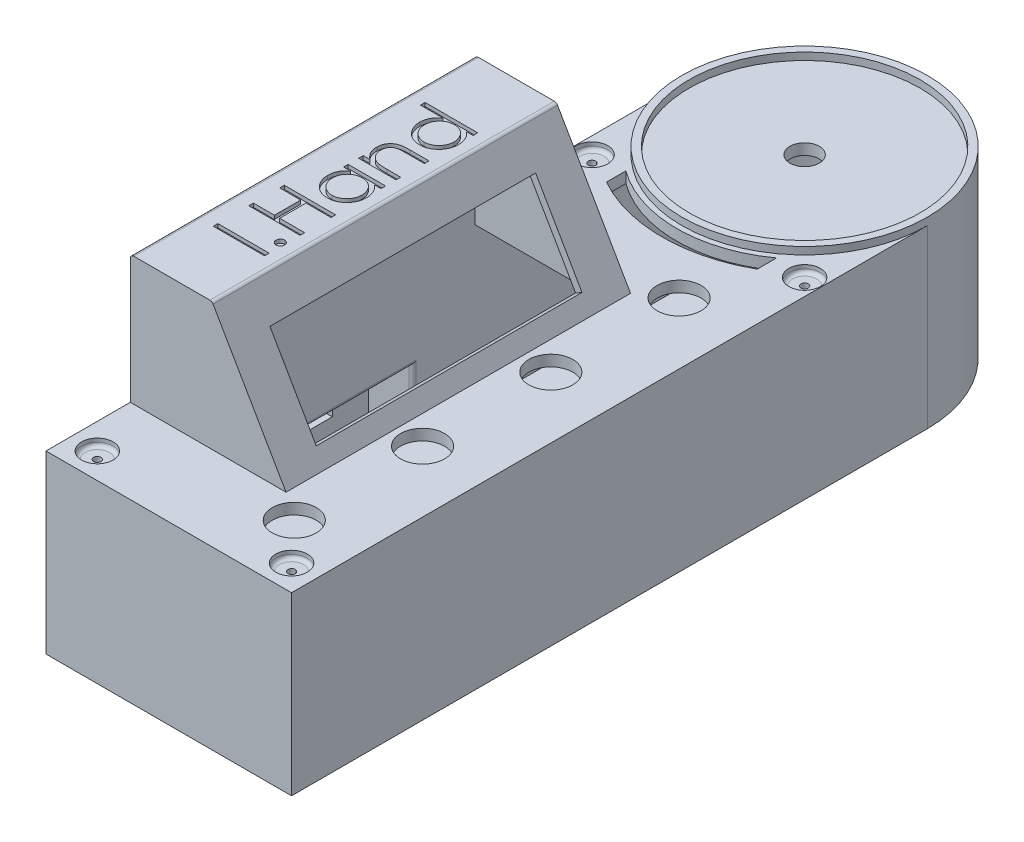
SolidWorks part; units mm, degrees
ref_plane "Front Plane" through (0, 0, 0) normal (0, 0, 1) x (1, 0, 0)
ref_plane "Top Plane" through (0, 0, 0) normal (0, 1, 0) x (1, 0, 0)
ref_plane "Right Plane" through (0, 0, 0) normal (1, 0, 0) x (0, 0, -1)
sketch "Sketch1" plane through (0, 0, 0) normal (0, 0, 1) x (1, 0, 0)
  line L6 (0, 0) -> (0, 47) construction
  line L8 (-31.5, 48) -> (-31.5, 50)
  line L9 (-31.5, 50) -> (-33.5, 50)
  line L10 (-33.5, 50) -> (-33.5, 0)
  line L11 (-33.5, 0) -> (0, 0)
  line L13 (0, 24.8) -> (-8.2, 24.8)
  line L14 (-31.5, 2) -> (-8.2, 2)
  line L17 (-31.5, 45) -> (-31.5, 2)
  line L18 (-8.2, 2) -> (-8.2, 24.8)
  line L19 (0, 0) -> (0, 24.8)
  line L20 (-4, 48) -> (-4, 45)
  line L23 (-31.5, 48) -> (-4, 48)
  line L24 (-31.5, 45) -> (-4, 45)
  dimension "D1" = 33.5
  dimension "D2" = 8
  dimension "D3" = 2
  dimension "D4" = 50
  dimension "D5" = 3
  dimension "D6" = 8.2
  dimension "D7" = 2
  dimension "D8" = 2
  dimension "D9" = 24.8
revolve "Revolve1" add sketch "Sketch1" angle 360 about L6
sketch "Sketch4" plane through (0, 0, 0) normal (0, 0, 1) x (1, 0, 0)
  line L3 (33.5, 0) -> (-33.5, 0)
  line L4 (-31.5, 45) -> (-31.5, 2)
  line L5 (-31.5, 2) -> (31.5, 2)
  line L6 (31.5, 2) -> (31.5, 45)
  line L7 (31.5, 45) -> (-31.5, 45)
  line L8 (31.5, 48) -> (33.5, 48)
  line L9 (-31.5, 48) -> (31.5, 48)
  line L10 (33.5, 48) -> (33.5, 0)
  line L11 (-31.5, 48) -> (-33.5, 48)
  line L12 (-33.5, 48) -> (-33.5, 0)
  dimension "D4" = 2
extrude "Boss-Extrude2" add sketch "Sketch4" along normal blind 173.5
sketch "Sketch6" plane through (0, 48, 0) normal (0, 1, 0) x (1, 0, 0)
  line L0 (4, 0) -> (-4, 0) construction
  circle A0 centre (0, 0) radius 4
extrude "Cut-Extrude1" cut sketch "Sketch6" against normal blind 3
sketch "Sketch9" plane through (0, 0, 173.5) normal (0, 0, 1) x (1, 0, 0)
  line L0 (-31.5, 45) -> (-31.5, 2)
  line L1 (-31.5, 2) -> (31.5, 2)
  line L2 (31.5, 2) -> (31.5, 45)
  line L3 (31.5, 45) -> (-31.5, 45)
extrude "Cut-Extrude2" cut sketch "Sketch9" against normal blind 173.5
sketch "Sketch10" plane through (0, 2, 0) normal (0, 1, 0) x (1, 0, 0)
  line L0 (-8.2, 0) -> (8.2, 0) construction
  circle A0 centre (0, 0) radius 8.2
extrude "Boss-Extrude3" add sketch "Sketch10" along normal blind 22.8
sketch "Sketch11" plane through (0, 0, 173.5) normal (0, 0, 1) x (1, 0, 0)
  line L1 (-31.5, 2) -> (31.5, 2)
  line L2 (-31.5, 2) -> (-31.5, 45)
  line L3 (-31.5, 45) -> (31.5, 45)
  line L4 (31.5, 2) -> (31.5, 45)
extrude "Boss-Extrude4" add sketch "Sketch11" against normal blind 2
sketch "Sketch13" plane through (0, 2, 0) normal (0, 1, 0) x (1, 0, 0)
  line L0 (-26.5, -161.5) -> (-26.5, -171.5)
  line L1 (-31.5, -171.5) -> (-21.5, -171.5)
  line L2 (-31.5, -171.5) -> (-31.5, -161.5)
  line L3 (-31.5, -161.5) -> (-21.5, -161.5)
  line L4 (-21.5, -171.5) -> (-21.5, -161.5)
  line L5 (31.5, -171.5) -> (21.5, -171.5)
  line L6 (31.5, -171.5) -> (31.5, -161.5)
  line L7 (31.5, -161.5) -> (21.5, -161.5)
  line L8 (21.5, -171.5) -> (21.5, -161.5)
  line L9 (-26.5, -171.5) -> (-21.5, -166.5)
  line L10 (-21.5, -166.5) -> (-31.5, -166.5)
  line L11 (26.5, -161.5) -> (26.5, -171.5)
  line L12 (26.5, -171.5) -> (21.5, -166.5)
  line L13 (21.5, -166.5) -> (31.5, -166.5)
  circle A0 centre (-26.5, -166.5) radius 3
  circle A1 centre (26.5, -166.5) radius 3
  dimension "D1" = 10
  dimension "D2" = 10
  dimension "D3" = 10
extrude "Boss-Extrude5" add sketch "Sketch13" along normal blind 43 contours A0 | A1
sketch "Sketch14" plane through (0, 2, 0) normal (0, 1, 0) x (1, 0, 0)
  circle A0 centre (-26.5, -166.5) radius 1
  circle A1 centre (26.5, -166.5) radius 1
extrude "Cut-Extrude3" cut sketch "Sketch14" along normal blind 46
sketch "Sketch15" plane through (0, 48, 0) normal (0, 1, 0) x (1, 0, 0)
  circle A0 centre (-26.5, -166.5) radius 4.3
  circle A1 centre (26.5, -166.5) radius 4.3
extrude "Cut-Extrude4" cut sketch "Sketch15" against normal blind 2
fillet "Fillet1" radius 1 2 edges at (26.5, 46, 170.8) (-26.5, 46, 170.8)
sketch "Sketch16" plane through (0, 48, 0) normal (0, 1, 0) x (1, 0, 0)
  line L0 (0, -173.5) -> (0, -33.5)
  line L1 (33.5, -173.5) -> (-33.5, -173.5) construction
  line L2 (0, -103.5) -> (-33.5, -103.5)
  line L3 (-33.5, -173.5) -> (-33.5, 0) construction
  line L4 (0, -103.5) -> (0, -150.5)
  line L5 (-29.9, -148.5) -> (-3.6, -148.5)
  line L6 (-29.9, -148.5) -> (-29.9, -58.5)
  line L7 (-29.9, -58.5) -> (-3.6, -58.5)
  line L8 (-3.6, -148.5) -> (-3.6, -58.5)
  line L9 (-29.9, -148.5) -> (-3.6, -58.5) construction
  line L10 (-29.9, -58.5) -> (-3.6, -148.5) construction
  line L11 (0, -150.5) -> (-33.5, -150.5)
  line L12 (-33.5, -150.5) -> (-33.5, -56.5)
  line L13 (-33.5, -56.5) -> (0, -56.5)
  line L14 (0, -56.5) -> (0, -103.5)
  arc A0 (-33.5, 0) -> (33.5, 0) centre (0, 0) ccw construction
  point P11 (-16.75, -103.5)
  dimension "D1" = 90
  dimension "D2" = 26.3
  dimension "D3" = 2
  dimension "D4" = 2
sketch "Sketch19" plane through (0, 48, 0) normal (0, 1, 0) x (1, 0, 0)
  line L0 (0, -173.5) -> (0, -33.5) construction
  line L1 (0, -173.5) -> (0, -33.5)
  line L2 (0, -103.5) -> (33.5, -103.5)
  line L3 (33.5, -173.5) -> (33.5, 0) construction
  line L4 (33.5, -103.5) -> (16.75, -103.5)
  line L5 (16.75, -103.5) -> (16.75, -68.5)
  line L7 (16.75, -68.5) -> (16.75, -33.5)
  line L8 (0, -68.5) -> (33.5, -68.5)
  line L9 (0, -138.5) -> (33.5, -138.5)
  line L10 (16.75, -103.5) -> (16.75, -138.5)
  line L11 (16.75, -138.5) -> (16.75, -173.5)
  line L12 (33.5, -173.5) -> (-33.5, -173.5) construction
  circle A0 centre (16.75, -51) radius 6
  circle A1 centre (16.75, -86) radius 6
  circle A2 centre (16.75, -121) radius 6
  circle A3 centre (16.75, -156) radius 6
extrude "Cut-Extrude5" cut sketch "Sketch19" against normal blind 3 contours A0 | A1 | A2 | A3
ref_plane "Plane2" through (0, 0, 56.5) normal (0, 0, 1) x (1, 0, 0)
sketch "Sketch20" plane through (0, 0, 56.5) normal (0, 0, 1) x (1, 0, 0)
  line L0 (9, 48) -> (-11.2073, 83)
  line L1 (0, 48) -> (-33.5, 48) construction
  line L3 (-33.5, 48) -> (9, 48)
  line L5 (5.5359, 50) -> (-12.362, 81)
  line L7 (-31.5, 50) -> (5.5359, 50)
  line L8 (-33.5, 48) -> (-33.5, 0) construction
  line L11 (-33.5, 48) -> (-33.5, 83)
  line L12 (-33.5, 83) -> (-11.2073, 83)
  line L13 (-31.5, 50) -> (-31.5, 81)
  line L14 (-31.5, 81) -> (-12.362, 81)
  dimension "D1" = 60
  dimension "D3" = 2
  dimension "D4" = 2
  dimension "D2" = 2
  dimension "D5" = 2
  dimension "D6" = 9
  dimension "D7" = 35
extrude "Boss-Extrude6" add sketch "Sketch20" along normal up to vertex (94 mm away) up to point (-33.5, 48, 150.5)
sketch "Sketch21" plane through (0, 50, 0) normal (0, 1, 0) x (1, 0, 0)
  line L1 (-31.5, -150.5) -> (5.5359, -150.5)
  line L2 (-31.5, -150.5) -> (-31.5, -56.5)
  line L3 (-31.5, -56.5) -> (5.5359, -56.5)
  line L4 (5.5359, -150.5) -> (5.5359, -56.5)
extrude "Cut-Extrude6" cut sketch "Sketch21" against normal blind 13
fillet "Fillet2" radius 1 2 edges at (-11.2073, 83, 103.5) (-33.5, 83, 103.5)
sketch "Sketch22" plane through (0, 0, 150.5) normal (0, 0, 1) x (1, 0, 0)
  line L1 (-33.5, 48) -> (-33.5, 45)
  line L2 (-33.5, 45) -> (9, 45)
  line L3 (9, 45) -> (9, 48)
  line L7 (9, 48) -> (-10.9186, 82.5)
  line L8 (-11.7846, 83) -> (-32.5, 83)
  line L9 (-33.5, 48) -> (-31.5, 48)
  line L10 (-11.7846, 83) -> (-32.5, 83)
  line L11 (-12.362, 81) -> (5.5359, 50)
  line L12 (5.5359, 50) -> (5.5359, 48)
  line L13 (5.5359, 48) -> (9, 48)
  line L14 (9, 48) -> (-10.9186, 82.5)
  line L27 (-33.5, 82) -> (-33.5, 48)
  line L28 (-33.5, 82) -> (-33.5, 48)
  line L29 (-31.5, 48) -> (-31.5, 81)
  line L31 (-31.5, 81) -> (-12.362, 81)
  arc A2 (-10.9186, 82.5) -> (-11.7846, 83) centre (-11.7846, 82) ccw
  arc A3 (-10.9186, 82.5) -> (-11.7846, 83) centre (-11.7846, 82) ccw
  arc A5 (-32.5, 83) -> (-33.5, 82) centre (-32.5, 82) ccw
  arc A6 (-32.5, 83) -> (-33.5, 82) centre (-32.5, 82) ccw
  dimension "D2" = 3
  dimension "D1" = 0
extrude "Boss-Extrude8" add sketch "Sketch22" against normal blind 2
sketch "Sketch23" plane through (27.5346, 15.8971, 0) normal (0.866, 0.5, 0) x (0, 0, -1)
  line L0 (-56.5, 37.0692) -> (-56.5, 76.9064) construction
  line L1 (-150.5, 37.0692) -> (-56.5, 37.0692)
  line L2 (-150.5, 37.0692) -> (-150.5, 67.8692)
  line L3 (-150.5, 67.8692) -> (-56.5, 67.8692)
  line L4 (-56.5, 37.0692) -> (-56.5, 67.8692)
  line L5 (-103.5, 41.5692) -> (-103.5, 67.8692)
  line L6 (-103.5, 67.8692) -> (-56.5, 52.4692)
  line L7 (-56.5, 52.4692) -> (-150.5, 52.4692)
  line L9 (-139.75, 42.0692) -> (-67.25, 42.0692)
  line L10 (-139.75, 42.0692) -> (-139.75, 67.3692)
  line L11 (-139.75, 67.3692) -> (-67.25, 67.3692)
  line L12 (-67.25, 42.0692) -> (-67.25, 67.3692)
  line L13 (-139.75, 42.0692) -> (-67.25, 67.3692) construction
  line L14 (-139.75, 67.3692) -> (-67.25, 42.0692) construction
  point P12 (-103.5, 54.7192)
  dimension "D1" = 94
  dimension "D2" = 72.5
  dimension "D3" = 5
  dimension "D4" = 25.3
extrude "Cut-Extrude7" cut sketch "Sketch23" against normal blind 2 contours L11 L12 L9 L10
sketch "Sketch24" plane through (0, 0, 56.5) normal (0, 0, -1) x (-1, 0, 0)
  line L12 (-9, 48) -> (-9, 45)
  line L13 (-9, 45) -> (33.5, 45)
  line L14 (33.5, 45) -> (33.5, 82)
  line L15 (32.5, 83) -> (11.7846, 83)
  line L16 (10.9186, 82.5) -> (-9, 48)
  arc A2 (33.5, 82) -> (32.5, 83) centre (32.5, 82) ccw
  arc A3 (11.7846, 83) -> (10.9186, 82.5) centre (11.7846, 82) ccw
extrude "Boss-Extrude9" add sketch "Sketch24" against normal blind 2
sketch "Sketch25" plane through (0, 48, 0) normal (0, 1, 0) x (1, 0, 0)
  line L0 (0, -173.5) -> (0, -33.5) construction
  line L1 (0, -173.5) -> (0, -33.5) construction
  line L2 (0, -33.5) -> (33.5, -33.5) construction
  line L3 (33.5, -173.5) -> (33.5, 0) construction
  line L4 (0, -33.5) -> (-33.5, -33.5) construction
  line L5 (-33.5, -56.5) -> (-33.5, 0) construction
  line L7 (-33.5, -33.5) -> (-24.5, -33.5) construction
  line L8 (-33.5, -33.5) -> (-33.5, -24.5) construction
  line L9 (-33.5, -24.5) -> (-24.5, -24.5) construction
  line L10 (-24.5, -33.5) -> (-24.5, -24.5) construction
  line L11 (33.5, -33.5) -> (24.5, -33.5) construction
  line L12 (33.5, -33.5) -> (33.5, -24.5) construction
  line L13 (33.5, -24.5) -> (24.5, -24.5) construction
  line L14 (24.5, -33.5) -> (24.5, -24.5) construction
  circle A0 centre (29, -29) radius 3
  circle A1 centre (-29, -29) radius 3
  dimension "D4" = 4.5
  dimension "D6" = 6
  dimension "D1" = 9
  dimension "D2" = 9
  dimension "D3" = 9
  dimension "D5" = 4.5
  dimension "D7" = 4.5
extrude "Boss-Extrude10" add sketch "Sketch25" against normal blind 48
sketch "Sketch26" plane through (0, 48, 0) normal (0, 1, 0) x (1, 0, 0)
  circle A0 centre (29, -29) radius 1
  circle A1 centre (-29, -29) radius 1
  dimension "D1" = 2
extrude "Cut-Extrude8" cut sketch "Sketch26" against normal blind 46
sketch "Sketch27" plane through (0, 48, 0) normal (0, 1, 0) x (1, 0, 0)
  circle A0 centre (-29, -29) radius 4.3
  circle A1 centre (29, -29) radius 4.3
  dimension "D1" = 8.6
extrude "Cut-Extrude9" cut sketch "Sketch27" against normal blind 2
fillet "Fillet3" radius 1 2 edges at (29, 46, 33.3) (-29, 46, 33.3)
sketch "Sketch29" plane through (-33.5, 0, 0) normal (-1, 0, 0) x (0, 0, 1)
  line L0 (103.5, 82) -> (103.5, 0)
  line L2 (173.5, 0) -> (0, 0) construction
  line L3 (73.5, 22) -> (73.5, 0)
  line L4 (73.5, 22) -> (133.5, 22)
  line L5 (73.5, 0) -> (133.5, 0)
  line L6 (133.5, 22) -> (133.5, 0)
  line L7 (73.5, 22) -> (133.5, 0) construction
  line L8 (73.5, 0) -> (133.5, 22) construction
  line L9 (75.5, 20) -> (75.5, 2)
  line L10 (75.5, 20) -> (131.5, 20)
  line L11 (75.5, 2) -> (131.5, 2)
  line L12 (131.5, 20) -> (131.5, 2)
  line L13 (75.5, 20) -> (131.5, 2) construction
  line L14 (75.5, 2) -> (131.5, 20) construction
  line L15 (150.5, 82) -> (56.5, 82) construction
  point P7 (103.5, 11)
  point P8 (103.5, 11)
  dimension "D1" = 22
  dimension "D2" = 60
  dimension "D3" = 0
  dimension "D4" = 2
  dimension "D5" = 2
  dimension "D6" = 2
  dimension "D7" = 2
  dimension "D8" = 0
sketch "Sketch30" plane through (-33.5, 0, 0) normal (-1, 0, 0) x (0, 0, 1)
  line L0 (75.5, 20) -> (75.5, 2) construction
  line L1 (75.5, 20) -> (131.5, 20) construction
  line L2 (75.5, 2) -> (131.5, 2) construction
  line L3 (131.5, 20) -> (131.5, 2) construction
  line L4 (131.5, 20) -> (131.5, 2)
  line L5 (75.5, 2) -> (131.5, 2)
  line L6 (75.5, 20) -> (75.5, 2)
  line L7 (75.5, 20) -> (131.5, 20)
extrude "Cut-Extrude10" cut sketch "Sketch30" against normal blind 2
sketch "Sketch31" plane through (-33.5, 0, 0) normal (-1, 0, 0) x (0, 0, 1)
  line L0 (131.5, 20) -> (131.5, 2) construction
  line L1 (133.5, 22) -> (133.5, 0) construction
  line L2 (75.5, 2) -> (131.5, 2) construction
  line L3 (73.5, 0) -> (133.5, 0) construction
  line L4 (75.5, 20) -> (75.5, 2) construction
  line L5 (75.5, 20) -> (131.5, 20) construction
  line L6 (73.5, 22) -> (73.5, 0) construction
  line L7 (73.5, 22) -> (133.5, 22) construction
  line L8 (131.5, 20) -> (131.5, 2)
  line L9 (133.5, 22) -> (133.5, 0)
  line L10 (75.5, 2) -> (131.5, 2)
  line L11 (73.5, 0) -> (133.5, 0)
  line L12 (75.5, 20) -> (75.5, 2)
  line L13 (75.5, 20) -> (131.5, 20)
  line L14 (73.5, 22) -> (73.5, 0)
  line L15 (73.5, 22) -> (133.5, 22)
extrude "Boss-Extrude11" add sketch "Sketch31" along normal blind 12
fillet "Fillet4" radius 1 3 edges at (-33.5, 11, 133.5) (-33.5, 22, 103.5) (-33.5, 11, 73.5)
sketch "Sketch33" plane through (-45.5, 0, 0) normal (-1, 0, 0) x (0, 0, 1)
  line L0 (131.5, 2) -> (131.5, 20) construction
  line L1 (75.5, 2) -> (131.5, 2) construction
  line L2 (75.5, 20) -> (75.5, 2) construction
  line L3 (131.5, 20) -> (75.5, 20) construction
  line L4 (131.5, 2) -> (131.5, 20)
  line L5 (75.5, 2) -> (131.5, 2)
  line L6 (75.5, 20) -> (75.5, 2)
  line L7 (131.5, 20) -> (75.5, 20)
extrude "Boss-Extrude12" add sketch "Sketch33" against normal blind 2
sketch "Sketch34" plane through (-88.691, 83, 0) normal (0, -1, 0) x (0, 0, -1)
  line L0 (-139.75, 73.9064) -> (-67.25, 73.9064) construction
  line L2 (-150.5, 76.9064) -> (-56.5, 76.9064) construction
  text T0 "I.Hand" font "Century Gothic" height 14
  dimension "D1" = 3
  dimension "D2" = 0
  dimension "D3" = 0
extrude "Cut-Extrude11" cut sketch "Sketch34" along normal blind 1
sketch "Sketch35" plane through (-45.5, 0, 0) normal (-1, 0, 0) x (0, 0, 1)
  line L1 (75.5, 2) -> (131.5, 2) construction
  line L2 (75.5, 2) -> (75.5, 20) construction
  line L3 (75.5, 20) -> (131.5, 20) construction
  line L4 (131.5, 2) -> (131.5, 20) construction
  line L5 (75.5, 2) -> (131.5, 20) construction
  line L6 (75.5, 20) -> (131.5, 2) construction
  line L7 (133.5, 22) -> (73.5, 22) construction
  line L8 (73.5, 0) -> (133.5, 0) construction
  line L9 (73.5, 22) -> (73.5, 0) construction
  line L10 (133.5, 0) -> (133.5, 22) construction
  line L11 (76.725, 7) -> (85.375, 7) construction
  line L13 (85.375, 7) -> (85.375, 19)
  line L14 (85.375, 19) -> (98.475, 19)
  line L15 (98.475, 19) -> (98.475, 7)
  line L16 (116.875, 7) -> (116.875, 18.8)
  line L17 (116.875, 18.8) -> (126.775, 18.8)
  line L18 (126.775, 18.8) -> (126.775, 7)
  line L19 (76.725, 7) -> (130.275, 7) construction
  line L20 (116.875, 7) -> (126.775, 7)
  line L21 (85.375, 7) -> (98.475, 7)
  point P0 (103.5, 11)
  point P24 (103.5, 7)
  dimension "D1" = 2
  dimension "D2" = 2
  dimension "D3" = 2
  dimension "D4" = 2
  dimension "D5" = 12
  dimension "D6" = 13.1
  dimension "D7" = 18.4
  dimension "D8" = 9.9
  dimension "D9" = 11.8
  dimension "D10" = 8.65
  dimension "D11" = 3.5
  dimension "D12" = 5
extrude "Cut-Extrude12" cut sketch "Sketch35" against normal blind 2
fillet "Fillet5" radius 1 3 edges at (-45.5, 11, 133.5) (-45.5, 11, 73.5) (-45.5, 22, 103.5)
sketch "Sketch36" plane through (0, 48, 0) normal (0, 1, 0) x (1, 0, 0)
  line L0 (0, -33.5) -> (0, -34.8932)
  line L1 (0, -34.8932) -> (0, -38.8932)
  line L2 (20.5725, -33.5) -> (20.5725, -28.2088)
  line L3 (-20.5725, -28.2088) -> (-20.5725, -33.5)
  arc A0 (-33.5, 0) -> (33.5, 0) centre (0, 0) ccw construction
  arc A1 (0, -34.8932) -> (-20.5725, -28.2088) centre (0, 0.1068) cw
  arc A2 (0, -34.8932) -> (20.5725, -28.2088) centre (0, 0.1068) ccw
  arc A3 (0, -38.8932) -> (-20.5725, -33.5) centre (0, 3.0408) cw
  arc A4 (0, -38.8932) -> (20.5725, -33.5) centre (0, 3.0408) ccw
  dimension "D1" = 5.2912
extrude "Cut-Extrude13" cut sketch "Sketch36" against normal blind 3 and the other way through all contours L1 A4 L2 A2 | A3 L1 A1 L3 region at (10.7626, 48, 34.8016) region at (-10.7626, 48, 34.8016)
fillet "Fillet6" radius 1 3 edges at (-31.5, 11, 75.5) (-31.5, 20, 103.5) (-31.5, 11, 131.5)
sketch "Sketch37" plane through (31.5, 0, 0) normal (-1, 0, 0) x (0, 0, 1)
  line L0 (30.6583, 33.5) -> (171.5, 33.5)
  line L1 (30.6583, 2) -> (30.6583, 45) construction
  line L2 (171.5, 2) -> (171.5, 45) construction
  line L3 (171.5, 45) -> (30.6583, 45) construction
  line L5 (30.6583, 33.5) -> (171.5, 33.5)
  line L6 (30.6583, 33.5) -> (30.6583, 31.4)
  line L7 (30.6583, 31.4) -> (171.5, 31.4)
  line L8 (171.5, 33.5) -> (171.5, 31.4)
  line L9 (30.6583, 35.5) -> (171.5, 35.5)
  line L10 (30.6583, 35.5) -> (30.6583, 29.4)
  line L11 (30.6583, 29.4) -> (171.5, 29.4)
  line L12 (171.5, 35.5) -> (171.5, 29.4)
  line M3 (30.6583, 45) -> (30.6583, 2)
  line M5 (171.5, 2) -> (171.5, 45)
  dimension "D1" = 11.5
  dimension "D2" = 2.1
  dimension "D3" = 2
  dimension "D4" = 2
extrude "Boss-Extrude13" add sketch "Sketch37" along normal blind 4 contours L9 L0 M3 M5 | L11 L7 M3 M5 region at (31.5, 34.5, 101.0792) region at (31.5, 30.4, 101.0792)
fillet "Fillet8" radius 2 1 edges at (31.5, 29.4, 101.0792)
ref_plane "Plane4" through (0, 45, 0) normal (0, -1, 0) x (-1, 0, 0)
